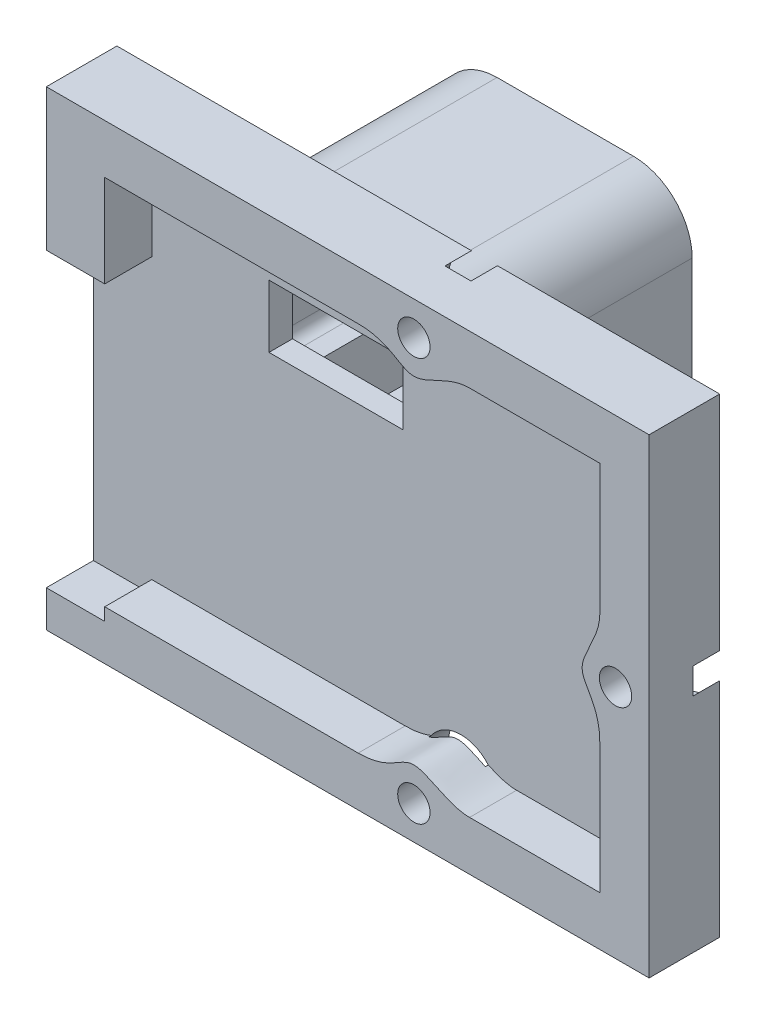
SolidWorks part; units mm, degrees
material "Nickel"
ref_plane "Front Plane" through (0, 0, 0) normal (0, 0, 1) x (1, 0, 0)
ref_plane "Top Plane" through (0, 0, 0) normal (0, 1, 0) x (1, 0, 0)
ref_plane "Right Plane" through (0, 0, 0) normal (1, 0, 0) x (0, 0, -1)
sketch "Sketch8" plane through (0, 0, 0) normal (0, 0, 1) x (1, 0, 0)
  line L5 (0.3, 6.858) -> (0.3, -6.858) construction
  line L12 (7.158, 0) -> (0.3, 0) construction
  line L17 (6.623, 1.8943) -> (6.623, 6.323)
  line L18 (6.623, 6.323) -> (2.1943, 6.323)
  line L19 (-1.5943, 6.323) -> (-10.214, 6.323)
  line L20 (-10.214, -6.323) -> (-10.214, 6.323)
  line L21 (0.3, 0) -> (-10.214, 0) construction
  line L22 (-1.5943, -6.323) -> (-10.214, -6.323)
  line L23 (6.623, -6.323) -> (2.1943, -6.323)
  line L24 (6.623, -1.8943) -> (6.623, -6.323)
  arc A32 (7.158, -1.3593) -> (7.158, 1.3593) centre (7.158, 0) ccw
  arc A33 (1.6593, 6.858) -> (-1.0593, 6.858) centre (0.3, 6.858) ccw
  arc A34 (7.158, 1.3593) -> (6.623, 1.8943) centre (7.158, 1.8943) cw
  arc A35 (2.1943, 6.323) -> (1.6593, 6.858) centre (2.1943, 6.858) cw
  arc A36 (-1.0593, 6.858) -> (-1.5943, 6.323) centre (-1.5943, 6.858) cw
  arc A37 (-1.0593, -6.858) -> (-1.5943, -6.323) centre (-1.5943, -6.858) ccw
  arc A38 (1.6593, -6.858) -> (-1.0593, -6.858) centre (0.3, -6.858) cw
  arc A39 (2.1943, -6.323) -> (1.6593, -6.858) centre (2.1943, -6.858) ccw
  arc A40 (7.158, -1.3593) -> (6.623, -1.8943) centre (7.158, -1.8943) ccw
  point P4 (0.3, 0)
  point P46 (2.9295, -21.7779)
  dimension "D7" = 8.6197
  dimension "D8" = 16.837
  dimension "D11" = 6.323
  dimension "D2" = 0.535
  dimension "D1" = 1.3593
  dimension "D3" = 1.3593
  dimension "D4" = 4.4287
sketch "Sketch9" plane through (0, 0, 0) normal (0, 0, 1) x (1, 0, 0)
  line L0 (0.3, 0) -> (0.3, -3) construction
  line L1 (-12.2, 8) -> (8.3, 8)
  line L2 (-2.7, 0) -> (3.3, 0) construction
  line L3 (8.3, 8) -> (8.3, -8)
  line L4 (-12.2, 8) -> (-12.2, -8)
  line L5 (-12.2, -8) -> (8.3, -8)
  point P0 (0.3, 0)
  point P7 (8.3, 0)
  dimension "D3" = 12.5
  dimension "D1" = 16
  dimension "D2" = 8
sketch "Sketch10" plane through (0, 0, 0) normal (0, 0, 1) x (1, 0, 0)
  line L1 (8.3, 8) -> (-12.2, 8)
  line L2 (8.3, 8) -> (8.3, -8)
  line L3 (8.3, -8) -> (-12.2, -8)
  line L4 (-12.2, 8) -> (-12.2, -8)
sketch "Sketch11" plane through (0, 0, 0) normal (0, 0, 1) x (1, 0, 0)
  line L0 (6.623, 6.323) -> (2.1943, 6.323)
  line L1 (8.3, 8) -> (-12.2, 8)
  line L2 (8.3, 8) -> (8.3, -8)
  line L3 (8.3, -8) -> (-12.2, -8)
  line L4 (-12.2, 8) -> (-12.2, -8)
  line L5 (-1.5943, 6.323) -> (-10.214, 6.323)
  line L6 (-10.214, -6.323) -> (-10.214, 6.323)
  line L7 (-10.214, -6.323) -> (-1.5943, -6.323)
  line L8 (6.623, -6.323) -> (2.1943, -6.323)
  line L9 (6.623, 6.323) -> (6.623, 1.8943)
  line L10 (6.623, -6.323) -> (6.623, -1.8943)
  line L11 (0.3, 6.858) -> (0.3, -6.858) construction
  line L12 (2.1943, 6.323) -> (-1.5943, 6.323) construction
  line L13 (7.158, 0) -> (0.3, 0) construction
  line L14 (6.623, 1.8943) -> (6.623, -1.8943) construction
  line L15 (2.1943, -6.323) -> (-1.5943, -6.323) construction
  spline S0 degree 3 poles (2.1943, 6.323) (1.4468, 6.323) (0.1263, 5.123) (-0.4994, 6.323) (-1.5943, 6.323) knots 0 0 0 0 0.5 1 1 1 1
  spline S1 degree 3 poles (6.623, 1.8943) (6.623, 1.1468) (5.423, -0.1737) (6.623, -0.7994) (6.623, -1.8943) knots 0 0 0 0 0.5 1 1 1 1
  spline S2 degree 3 poles (2.1943, -6.323) (1.4468, -6.323) (0.1263, -5.123) (-0.4994, -6.323) (-1.5943, -6.323) knots 0 0 0 0 0.5 1 1 1 1
  dimension "D2" = 0.6
  dimension "D1" = 0.6
  dimension "D3" = 0.6
extrude "Boss-Extrude4" add sketch "Sketch11" along normal blind 1.6
extrude "Boss-Extrude5" add sketch "Sketch10" against normal blind 0.8
sketch "Sketch12" plane through (0, 0, -0.8) normal (0, 0, -1) x (-1, 0, 0)
  circle A0 centre (-0.3, 6.858) radius 1.225
  circle A1 centre (-7.158, 0) radius 1.225
  circle A2 centre (-0.3, -6.858) radius 1.225
  dimension "D1" = 2.45
  dimension "D2" = 2.45
  dimension "D3" = 2.45
extrude "Cut-Extrude1" cut sketch "Sketch12" against normal offset from surface (0.9 mm away) 1.5 up to face at (-1.95, 0, 1.6)
sketch "Sketch13" plane through (0, 0, 0.1) normal (0, 0, -1) x (-1, 0, 0)
  circle A0 centre (-0.3, 6.858) radius 0.55
  circle A1 centre (-7.158, 0) radius 0.55
  circle A2 centre (-0.3, -6.858) radius 0.55
  dimension "D1" = 1.1
  dimension "D2" = 1.1
  dimension "D3" = 1.1
extrude "Cut-Extrude2" cut sketch "Sketch13" against normal up to surface (1.5 mm away) up to face at (-1.95, 0, 1.6)
sketch "Sketch14" plane through (0, 0, -0.8) normal (0, 0, -1) x (-1, 0, 0)
  line L10 (1.5943, -6.323) -> (10.214, -6.323) construction
  line L11 (1.678, 2.362) -> (6.228, 2.362)
  line L12 (1.678, 2.362) -> (1.678, 4.492)
  line L13 (1.678, 4.492) -> (6.228, 4.492)
  line L14 (6.228, 2.362) -> (6.228, 4.492)
  line L15 (1.678, 2.362) -> (6.228, 4.492) construction
  line L16 (1.678, 4.492) -> (6.228, 2.362) construction
  line L17 (10.214, -6.323) -> (10.214, 6.323) construction
  point P0 (3.953, 3.427)
  dimension "D1" = 9.75
  dimension "D2" = 6.261
  dimension "D3" = 4.55
  dimension "D4" = 2.13
extrude "Cut-Extrude3" cut sketch "Sketch14" against normal up to surface (0.8 mm away) up to face at (1.2847, -0.058, 0)
sketch "Sketch15" plane through (0, 0, -0.8) normal (0, 0, -1) x (-1, 0, 0)
  line L0 (-0.022, 3.427) -> (7.928, 3.427) construction
  line L1 (1.678, 2.362) -> (1.678, 4.492) construction
  line L2 (6.228, 2.362) -> (6.228, 4.492) construction
  line L4 (1.478, 2.327) -> (-1.522, 2.327)
  line L5 (1.478, 2.327) -> (1.478, 4.527)
  line L6 (1.478, 4.527) -> (-1.522, 4.527)
  line L7 (-1.522, 2.327) -> (-1.522, 4.527)
  line L8 (1.478, 2.327) -> (-1.522, 4.527) construction
  line L9 (1.478, 4.527) -> (-1.522, 2.327) construction
  line L10 (9.428, 2.327) -> (6.428, 2.327)
  line L11 (9.428, 2.327) -> (9.428, 4.527)
  line L12 (9.428, 4.527) -> (6.428, 4.527)
  line L13 (6.428, 2.327) -> (6.428, 4.527)
  line L14 (9.428, 2.327) -> (6.428, 4.527) construction
  line L15 (9.428, 4.527) -> (6.428, 2.327) construction
  dimension "D1" = 1.7
  dimension "D2" = 1.7
  dimension "D3" = 2.2
  dimension "D4" = 2.2
  dimension "D5" = 3
  dimension "D6" = 3
sketch "Sketch17" plane through (0, 0, 1.6) normal (0, 0, 1) x (1, 0, 0)
  line L2 (-12.2, 8) -> (-12.2, -8) construction
  line L5 (-10.214, 6.323) -> (-10.214, -6.323) construction
  line L7 (-10.214, -6.7547) -> (-12.2, -6.7547)
  line L8 (-10.214, 6.323) -> (-10.214, -6.323) construction
  line L9 (-12.2, -6.7547) -> (-12.2, 3.1854)
  line L10 (-12.2, 3.1854) -> (-10.214, 3.1854)
  line L11 (-10.214, 3.1854) -> (-10.214, -6.7547)
extrude "Cut-Extrude5" cut sketch "Sketch17" against normal blind 1.6
sketch "Sketch18" plane through (0, 0, -0.8) normal (0, 0, -1) x (-1, 0, 0)
  line L0 (-0.3645, 6.538) -> (-0.3645, -1.184)
  line L1 (-0.3645, -1.184) -> (8.2705, -1.184)
  line L2 (8.2705, -1.184) -> (8.2705, 6.538)
  line L3 (8.2705, 6.538) -> (-0.3645, 6.538)
  line L4 (0.6355, 5.538) -> (0.6355, 1.316)
  line L5 (0.6355, 1.316) -> (7.2705, 1.316)
  line L6 (7.2705, 1.316) -> (7.2705, 5.538)
  line L7 (7.2705, 5.538) -> (0.6355, 5.538)
  line L8 (1.678, 3.427) -> (6.228, 3.427) construction
  line L9 (1.678, 4.492) -> (1.678, 2.362) construction
  line L10 (6.228, 2.362) -> (6.228, 4.492) construction
  line L11 (0.6355, 3.427) -> (7.2705, 3.427) construction
  point P20 (3.953, 3.427)
  point P21 (3.953, 3.427)
  dimension "D1" = 1
  dimension "D2" = 1
  dimension "D3" = 1
  dimension "D4" = 2.5
  dimension "D5" = 6.635
  dimension "D6" = 4.222
extrude "Boss-Extrude6" add sketch "Sketch18" along normal blind 7
ref_plane "Plane1" through (0, 0, -6.21) normal (0, 0, -1) x (-1, 0, 0)
fillet "Fillet2" radius 0.4 4 edges at (-0.6355, 1.316, -4.3) (-7.2705, 1.316, -4.3) (-7.2705, 5.538, -4.3) (-0.6355, 5.538, -4.3)
fillet "Fillet3" radius 2 4 edges at (-8.2705, -1.184, -4.3) (0.3645, -1.184, -4.3) (-8.2705, 6.538, -4.3) (0.3645, 6.538, -4.3)
sketch "Sketch19" plane through (0, 0, -7.8) normal (0, 0, -1) x (-1, 0, 0)
  line L0 (0.6355, 3.427) -> (7.2705, 3.427) construction
  line L1 (0.6355, 5.138) -> (0.6355, 1.716) construction
  line L2 (7.2705, 1.716) -> (7.2705, 5.138) construction
  line L3 (3.953, 3.427) -> (3.953, -2.4337) construction
  line L4 (1.0355, 1.316) -> (6.8705, 1.316) construction
  line L5 (1.703, 1.316) -> (6.203, 1.316)
  line L6 (6.203, 1.316) -> (6.203, -0.064)
  line L7 (1.703, 1.316) -> (1.703, -0.064)
  line L8 (1.703, -0.064) -> (6.203, -0.064)
  point P8 (3.953, 1.316)
  point P14 (3.953, 1.316)
  dimension "D1" = 4.5
  dimension "D2" = 1.38
extrude "Cut-Extrude6" cut sketch "Sketch19" against normal up to surface (7 mm away) up to face at (-3.953, 3.427, -0.8)
sketch "Sketch21" plane through (0, 0, -6.21) normal (0, 0, -1) x (-1, 0, 0)
  line L0 (1.703, -0.064) -> (1.703, -0.864)
  line L1 (1.703, -0.864) -> (6.203, -0.864)
  line L2 (6.203, -0.864) -> (6.203, -0.064)
  line L3 (6.203, -0.064) -> (1.703, -0.064)
  dimension "D1" = 0.8
extrude "Cut-Extrude7" cut sketch "Sketch21" against normal up to surface (5.41 mm away) up to face at (-1.2188, 1.7637, -0.8)
